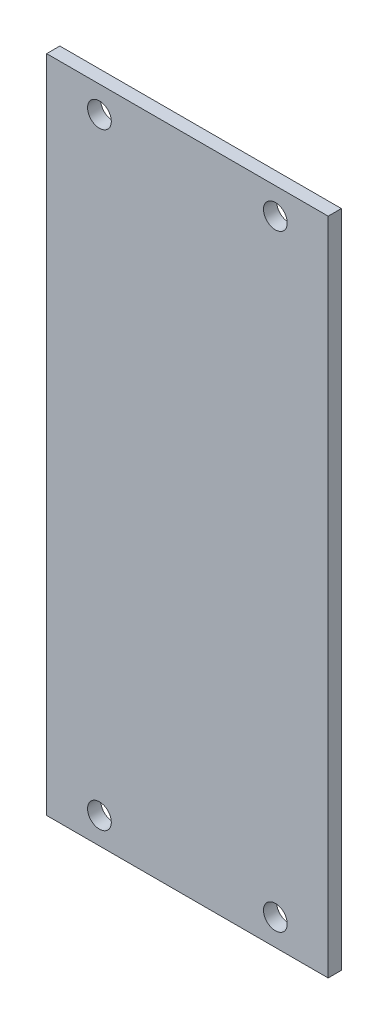
SolidWorks part; units mm, degrees
material "ABS"
ref_plane "Front Plane" through (0, 0, 0) normal (0, 0, 1) x (1, 0, 0)
ref_plane "Top Plane" through (0, 0, 0) normal (0, 1, 0) x (1, 0, 0)
ref_plane "Right Plane" through (0, 0, 0) normal (1, 0, 0) x (0, 0, -1)
sketch "Sketch1" plane through (0, 0, 0) normal (0, 0, 1) x (1, 0, 0)
  line L0 (26, 20) -> (26, -130) construction
  line L1 (0, 0) -> (52, 0)
  line L2 (0, 0) -> (0, -110)
  line L3 (0, -110) -> (52, -110)
  line L4 (52, 0) -> (52, -110)
  line L5 (-6, 20) -> (58, 20)
  line L6 (-6, 20) -> (-6, -130)
  line L7 (-6, -130) -> (58, -130)
  line L8 (58, 20) -> (58, -130)
  line L9 (-6, -55) -> (58, -55) construction
  circle A0 centre (6, 14) radius 2.6993
  circle A1 centre (46, 14) radius 2.6993
  circle A2 centre (46, -124) radius 2.6993
  circle A3 centre (6, -124) radius 2.6993
  point P9 (26, -130)
  point P10 (26, -110)
  point P11 (-6, -55)
  point P12 (0, -55)
  dimension "D1" = 52
  dimension "D2" = 110
  dimension "D3" = 64
  dimension "D4" = 150
  dimension "D5" = 12
  dimension "D6" = 6
extrude "Boss-Extrude1" add sketch "Sketch1" along normal blind 3 contours L8 L5 L6 L7 A1 A0 L1 L4 L3 L2 A2 A3 | L4 L1 L2 L3 region at (26, -55, 0) region at (26, 18.3692, 0)
equation "\"Depth\"= 90mm"
equation "\"Height\" = 150mm"
equation "\"Width\"= 64mm"
equation "\"D3@Sketch1\"=\"Width\""
equation "\"D4@Sketch1\"=\"Height\""
